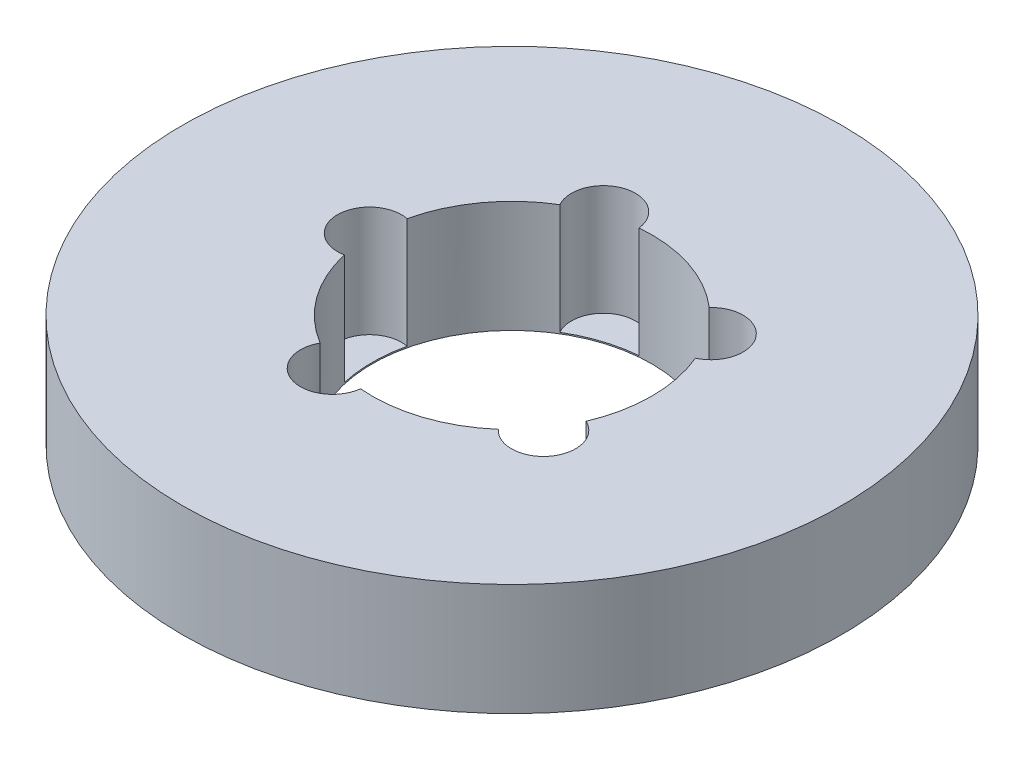
SolidWorks part; units mm, degrees
ref_plane "Front Plane" through (0, 0, 0) normal (0, 0, 1) x (1, 0, 0)
ref_plane "Top Plane" through (0, 0, 0) normal (0, 1, 0) x (1, 0, 0)
ref_plane "Right Plane" through (0, 0, 0) normal (1, 0, 0) x (0, 0, -1)
sketch "Sketch1" plane through (0, 0, 0) normal (0, 1, 0) x (1, 0, 0)
  circle A0 centre (0, 0) radius 82.5
  dimension "FLANGE_OD" = 165
extrude "Boss-Extrude1" add sketch "Sketch1" along normal blind 28
sketch "Sketch2" plane through (0, 0, 0) normal (0, 1, 0) x (1, 0, 0)
  circle A0 centre (0, 0) radius 35
  dimension "BORE_D" = 70
extrude "Cut-Extrude1" cut sketch "Sketch2" along normal through all
sketch "Sketch3" plane through (0, 28, 0) normal (0, 1, 0) x (1, 0, 0)
  circle A0 centre (0, 0) radius 35.6656 construction
  circle A1 centre (-35.6656, 0) radius 8.0205
  dimension "BOLT_D" = 16.0411
  dimension "BOLT_PCD" = 71.3313
extrude "Cut-Extrude2" cut sketch "Sketch3" against normal blind 27.6747
pattern_circular "CirPattern1" count 5 over 360 about axis through (0, 0, 0) along (0, 1, 0) of "Cut-Extrude2"
